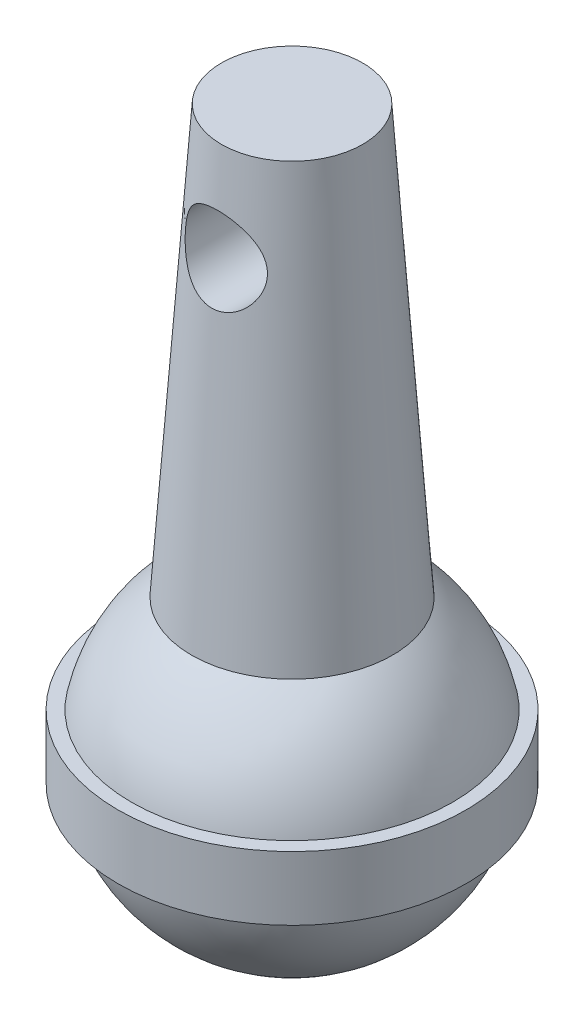
SolidWorks part; units mm, degrees
ref_plane "Plan de face" through (0, 0, 0) normal (0, 0, 1) x (1, 0, 0)
ref_plane "Plan de dessus" through (0, 0, 0) normal (0, 1, 0) x (1, 0, 0)
ref_plane "Plan de droite" through (0, 0, 0) normal (1, 0, 0) x (0, 0, -1)
sketch "Esquisse1" plane through (0, 0, 0) normal (0, 0, 1) x (1, 0, 0)
  line L0 (0, 20) -> (0, -20)
  arc A0 (0, 20) -> (0, -20) centre (0, 0) ccw
  dimension "D1" = 40
revolve "Révolution1" add sketch "Esquisse1" angle 360 about L0
sketch "Esquisse10" plane through (0, 0, 0) normal (0, 1, 0) x (1, 0, 0)
  circle A0 centre (0, 0) radius 13.3804
extrude "Boss.-Extru.1" add sketch "Esquisse10" along normal blind 68 draft 4
sketch "Esquisse11" plane through (0, 0, 0) normal (0, 0, 1) x (1, 0, 0)
  circle A0 centre (0, 56.2625) radius 5
extrude "Enlèv. mat.-Extru.1" cut sketch "Esquisse11" along normal blind 68 and the other way blind 68
sketch "Esquisse12" plane through (0, 0, 0) normal (1, 0, 0) x (0, 0, -1)
  line L1 (-21.2484, -3.9037) -> (-18.7516, -3.9037)
  line L2 (-21.2484, -3.9037) -> (-21.2484, 3.9037)
  line L3 (-21.2484, 3.9037) -> (-18.7516, 3.9037)
  line L4 (-18.7516, -3.9037) -> (-18.7516, 3.9037)
  line L5 (-21.2484, -3.9037) -> (-18.7516, 3.9037) construction
  line L6 (-21.2484, 3.9037) -> (-18.7516, -3.9037) construction
  arc A0 (-12.2763, 15.789) -> (12.2763, 15.789) centre (0, 0) ccw construction
  point P0 (-20, 0)
sketch "Esquisse19" plane through (0, 0, 0) normal (0, 1, 0) x (1, 0, 0)
  circle A0 centre (0, 0) radius 20
sweep "Balayage1" add profiles "Esquisse12" path "Esquisse19"
